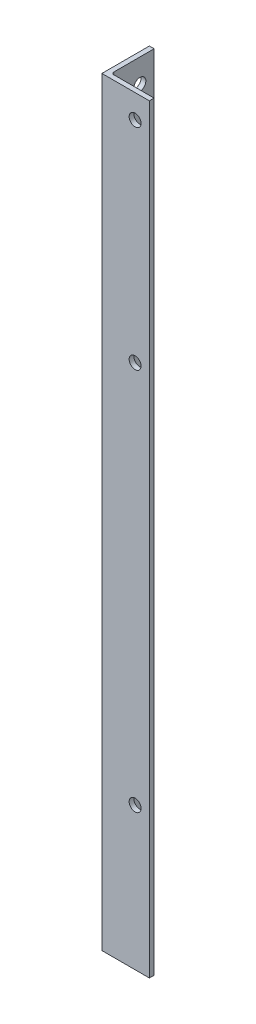
SolidWorks part; units mm, degrees
ref_plane "Front Plane" through (0, 0, 0) normal (0, 0, 1) x (1, 0, 0)
ref_plane "Top Plane" through (0, 0, 0) normal (0, 1, 0) x (1, 0, 0)
ref_plane "Right Plane" through (0, 0, 0) normal (1, 0, 0) x (0, 0, -1)
sketch "Sketch2" plane through (0, 0, 0) normal (0, 1, 0) x (1, 0, 0)
  line L0 (0, 31.75) -> (3.175, 31.75)
  line L1 (3.175, 31.75) -> (3.175, 4.7625)
  line L2 (4.7625, 3.175) -> (31.75, 3.175)
  line L3 (31.75, 3.175) -> (31.75, 0)
  line L4 (31.75, 0) -> (0, 0)
  line L5 (0, 0) -> (0, 31.75)
  arc A0 (3.175, 4.7625) -> (4.7625, 3.175) centre (4.7625, 4.7625) ccw
  point P9 (1.5875, 31.75)
  point P10 (31.75, 1.5875)
  dimension "D5" = 3.175
  dimension "D1" = 31.75
  dimension "D2" = 31.75
  dimension "D3" = 3.175
  dimension "D4" = 3.175
extrude "Boss-Extrude1" add sketch "Sketch2" along normal blind 508
sketch "RightSideHoles-Sketch3" plane through (0, 0, 0) normal (0, 0, 1) x (1, 0, 0)
  line L0 (0, 0) -> (31.75, 0) construction
  line L1 (0, 508) -> (31.75, 508) construction
  line L3 (0, 508) -> (0, 0) construction
  circle A0 centre (22.225, 95.4) radius 4
  circle A6 centre (22.225, 492.125) radius 4
  circle A9 centre (22.225, 351.5849) radius 4
  dimension "D3" = 8
  dimension "D1" = 95.4
  dimension "D2" = 22.225
  dimension "D10" = 351.5849
  dimension "D8" = 15.875
sketch "FrontSideHoles-Sketch4" plane through (0, 0, 0) normal (-1, 0, 0) x (0, 0, 1)
  line L0 (-31.75, 508) -> (0, 508) construction
  line L1 (0, 508) -> (0, 0) construction
  line L3 (-31.75, 0) -> (0, 0) construction
  circle A0 centre (-22.225, 95.4) radius 4
  circle A4 centre (-22.225, 492.125) radius 4
  circle A8 centre (-17.4625, 406.1349) radius 2
  circle A9 centre (-17.4625, 365.9349) radius 2
  dimension "D2" = 22.225
  dimension "D4" = 8
  dimension "D16" = 4
  dimension "D6" = 15.875
  dimension "D9" = 40.2
  dimension "D10" = 17.4625
  dimension "D3" = 95.4
  dimension "D8" = 406.1349
extrude "RightSideHoles-Cut-Extrude1" cut sketch "RightSideHoles-Sketch3" against normal blind 3.175
extrude "FrontSideHoles-Cut-Extrude2" cut sketch "FrontSideHoles-Sketch4" against normal blind 3.175
equation "\"RailThickness\"= .125in'Spec"
equation "\"VSWidth\"= 1.25in'Spec"
equation "\"VSHeight\"= 1.25in'Spec"
equation "\"VSLength\"= 20.0in"
equation "\"HoleOffsetFromEdge\"= \"RailThickness\" * 2.5"
equation "\"VSBottomSideRailHoleYFromBottomOfLowerRailYSValue\"= 95.4mm"
equation "\"VSTopSideRailHoleYFromEdge\"= \"TopRailHeight\" / 2"
equation "\"D1@RightSideHoles-Sketch3\" = \"VSBottomSideRailHoleYFromBottomOfLowerRailYSValue\""
equation "\"D2@RightSideHoles-Sketch3\"=\"FrameFastenerHoleOffsetFromSide\""
equation "\"D1@Boss-Extrude1\"=\"VSLength\""
equation "\"D4@FrontSideHoles-Sketch4\"=\"FrameFastenerHoleDiameter\""
equation "\"D6@FrontSideHoles-Sketch4\" = \"VSTopSideRailHoleYFromEdge\""
equation "\"VSMidSideRailHoleYFromV8TopOfMidSideRailYSValue\"= 351.58487mm"
equation "\"D2@Sketch2\"=\"VSWidth\""
equation "\"D1@Sketch2\"=\"VSHeight\""
equation "\"TopRailHeight\"= 1.25in"
equation "\"20TGT2PulleyWidth\"= 8.7mm'The STL of the Pulley in the diagram is a bit larger"
equation "\"D9@FrontSideHoles-Sketch4\"=\"VSBeltTensionerHoleY2FromY1YSValue\""
equation "\"VSBeltTensionerHoleY1ToAlignedWithYAxisGantryBlockUpperPulleyYSValue\"= 406.13487mm"
equation "\"VSBeltTensionerHoleY2FromY1YSValue\"= 40.2mm"
equation "\"D10@RightSideHoles-Sketch3\"=\"VSMidSideRailHoleYFromV8TopOfMidSideRailYSValue\""
equation "\"BeltTensionerMountingHoleOffsetFromEdge\"= \"HoleOffsetFromEdge\" + \"RailThickness\" * 2"
equation "\"VSBeltTensionerXMountingHoleOffsetFromSide\"= \"BeltTensionerMountingHoleOffsetFromEdge\" + \"RailThickness\""
equation "\"D10@FrontSideHoles-Sketch4\"=\"VSBeltTensionerXMountingHoleOffsetFromSide\""
equation "\"D3@FrontSideHoles-Sketch4\"=\"VSBottomSideRailHoleYFromBottomOfLowerRailYSValue\""
equation "\"D8@RightSideHoles-Sketch3\"=\"VSTopSideRailHoleYFromEdge\""
equation "\"BeltTensionerMountingHoleDiameter\"= 4.0mm"
equation "\"D16@FrontSideHoles-Sketch4\"=\"BeltTensionerMountingHoleDiameter\""
equation "\"D8@FrontSideHoles-Sketch4\"=\"VSBeltTensionerHoleY1ToAlignedWithYAxisGantryBlockUpperPulleyYSValue\""
equation "\"FrameFastenerHoleDiameter\"= 8mm"
equation "\"FrameFastenerHoleOffsetFromSide\"= \"VSWidth\" / 2 + \"GapBetweenVerticalSupportsAndRails\""
equation "\"D3@RightSideHoles-Sketch3\"=\"FrameFastenerHoleDiameter\""
equation "\"D2@FrontSideHoles-Sketch4\"=\"FrameFastenerHoleOffsetFromSide\""
equation "\"D5@Sketch2\"=\"RailThickness\""
equation "\"GapBetweenVerticalSupportsAndRails\"= \"RailThickness\" * 2"
